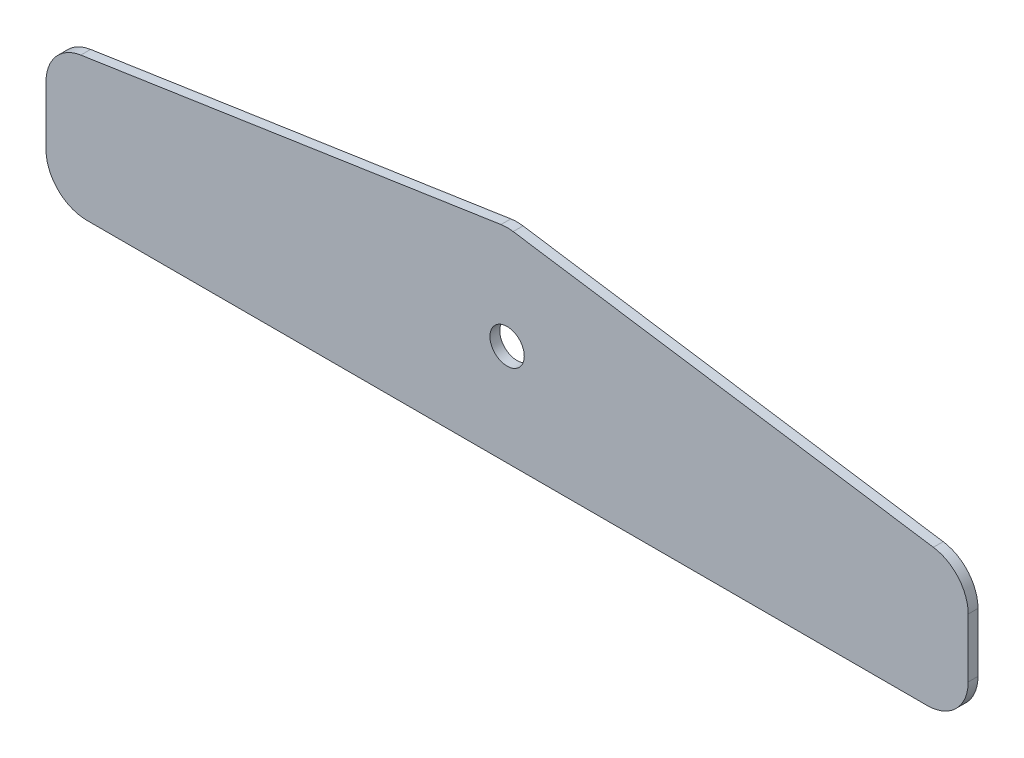
SolidWorks part; units mm, degrees
ref_plane "Front Plane" through (0, 0, 0) normal (0, 0, 1) x (1, 0, 0)
ref_plane "Top Plane" through (0, 0, 0) normal (0, 1, 0) x (1, 0, 0)
ref_plane "Right Plane" through (0, 0, 0) normal (1, 0, 0) x (0, 0, -1)
sketch "Sketch1" plane through (0, 0, 0) normal (0, 0, 1) x (1, 0, 0)
  line L2 (-56.4, 131.1383) -> (-56.4, 114.6383)
  line L3 (-56.4, 114.6383) -> (56.4, 114.6383)
  line L4 (56.4, 131.1383) -> (56.4, 114.6383)
  line L7 (0, 139.6383) -> (-56.4, 131.1383)
  line L8 (0, 139.6383) -> (56.4, 131.1383)
  line L11 (-56.4, 28.6363) -> (-56.4, 107.5) construction
  line L13 (56.4, 118.4479) -> (56.4, 103.4479) construction
  circle A0 centre (0, 127) radius 2.1 construction
  circle A1 centre (0, 127) radius 2.1
  point P3 (56.4, 98.4479)
  point P6 (0, 0)
  point P8 (56.4, 126.6392)
  point P9 (61.6843, 98.4479)
  point P10 (56.4, 95.6939)
  point P13 (-56.4, 127)
  point P14 (-56.4, 123.8138)
  point P15 (56.4, 107.0645)
  point P16 (0.428, 138.8104)
  point P17 (0, 0)
  point P23 (56.4, 106.0046)
  dimension "D1" = 25
  dimension "D2" = 16.5
  dimension "D3" = 4
extrude "Boss-Extrude1" add sketch "Sketch1" along normal blind 1.2
fillet "Fillet1" radius 5 5 edges at (56.4, 114.6383, 0.6) (-56.4, 114.6383, 0.6) (56.4, 131.1383, 0.6) (0, 139.6383, 0.6) (-56.4, 131.1383, 0.6)
